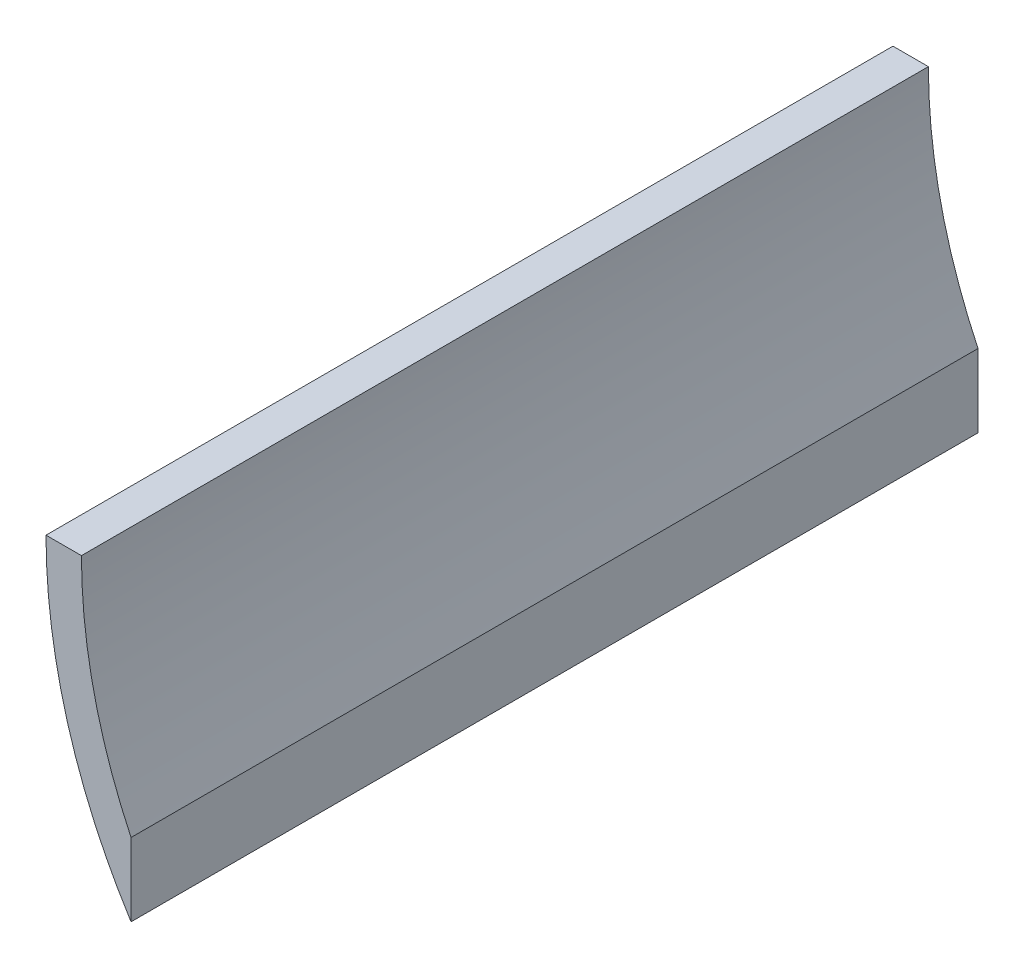
SolidWorks part; units mm, degrees
material "that blue high density foam"
ref_plane "Front" through (0, 0, 0) normal (0, 0, 1) x (1, 0, 0)
ref_plane "Top" through (0, 0, 0) normal (0, 1, 0) x (1, 0, 0)
ref_plane "Right" through (0, 0, 0) normal (1, 0, 0) x (0, 0, -1)
sketch "Sketch1" plane through (0, 0, 0) normal (0, 0, 1) x (1, 0, 0)
  line L0 (-82, -60.7866) -> (-82, -67.7866) construction
  line L2 (-82, -47.1761) -> (-82, -67.7866)
  line L3 (-96, 14.7134) -> (-106, 14.7134)
  arc A0 (-106, 14.7134) -> (-82, -67.7866) centre (47.7969, 14.7134) ccw construction
  arc A1 (-106, 14.7134) -> (-82, -67.7866) centre (47.7969, 14.7134) ccw
  arc A2 (-96, 14.7134) -> (-82, -47.1761) centre (47.7969, 14.7134) ccw
  dimension "D1" = 10
extrude "Boss-Extrude1" add sketch "Sketch1" along normal up to surface (239 mm away)
